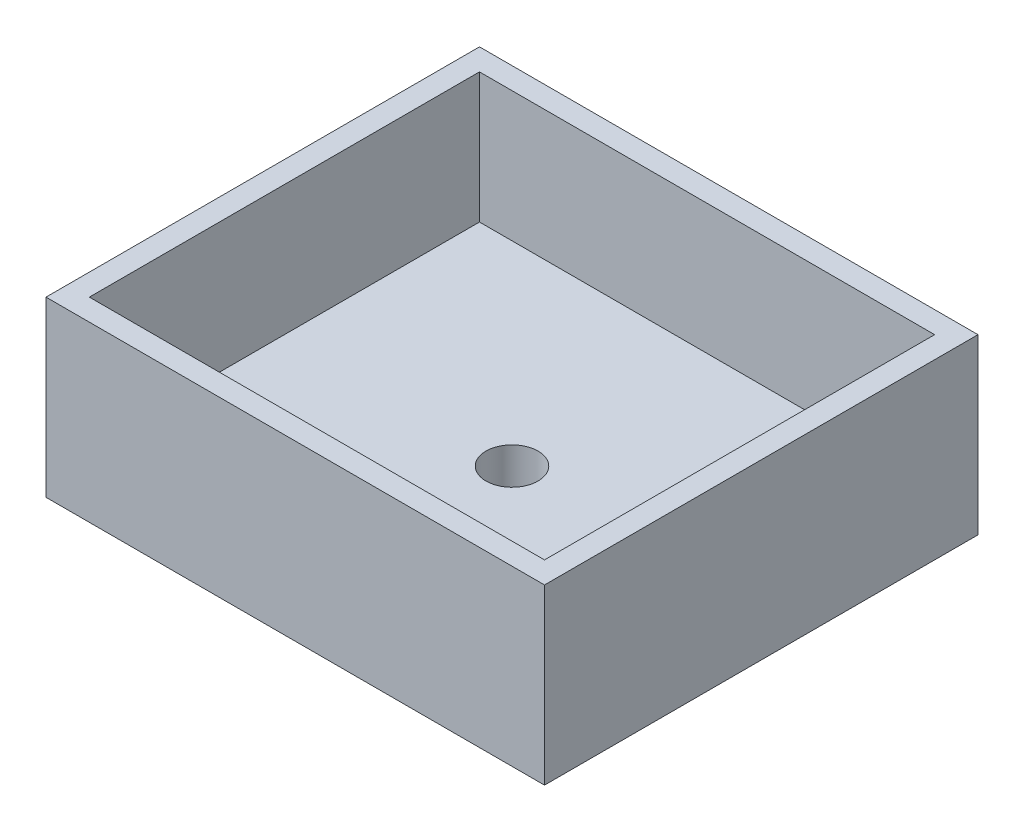
SolidWorks part; units mm, degrees
ref_plane "Front Plane" through (0, 0, 0) normal (0, 0, 1) x (1, 0, 0)
ref_plane "Top Plane" through (0, 0, 0) normal (0, 1, 0) x (1, 0, 0)
ref_plane "Right Plane" through (0, 0, 0) normal (1, 0, 0) x (0, 0, -1)
sketch "Sketch2" plane through (0, 0, 0) normal (0, 1, 0) x (1, 0, 0)
  line L0 (0, 20.2453) -> (0, -25.1679) construction
  line L1 (0, 0) -> (11.5, 0)
  line L2 (11.5, 0) -> (11.5, 10)
  line L3 (11.5, 10) -> (0, 10)
  line L4 (0, 10) -> (0, 0)
  line L5 (5.75, 10) -> (5.75, 0) construction
  line L6 (0, 5) -> (11.5, 5) construction
  line L8 (0.5, 0.5) -> (11, 0.5)
  line L9 (0.5, 0.5) -> (0.5, 9.5)
  line L10 (0.5, 9.5) -> (11, 9.5)
  line L11 (11, 0.5) -> (11, 9.5)
  line L12 (0.5, 0.5) -> (11, 9.5) construction
  line L13 (0.5, 9.5) -> (11, 0.5) construction
  point P11 (5.75, 5)
  dimension "D1" = 11.5
  dimension "D2" = 10
  dimension "D3" = 9
  dimension "D4" = 10.5
extrude "Boss-Extrude2" add sketch "Sketch2" along normal blind 1 contours L8 L11 L10 L9 region at (5.75, 0, -5)
extrude "Boss-Extrude3" add sketch "Sketch2<3>" along normal blind 4
sketch "Sketch2<3>" plane through (0, 0, 0) normal (0, 1, 0) x (1, 0, 0) same geometry as "Sketch2"
sketch "Sketch3" plane through (0, 1, 0) normal (0, 1, 0) x (1, 0, 0)
  line L0 (0.5, 5) -> (11, 5) construction
  line L1 (0.5, 0.5) -> (0.5, 9.5) construction
  line L2 (11, 0.5) -> (11, 9.5) construction
  line L3 (5.75, 9.5) -> (5.75, 0.5) construction
  line L4 (0.5, 9.5) -> (11, 9.5) construction
  line L5 (0.5, 0.5) -> (11, 0.5) construction
  circle A0 centre (5.75, 5) radius 0.6
  dimension "D1" = 1.2
extrude "Cut-Extrude1" cut sketch "Sketch3" against normal blind 10
